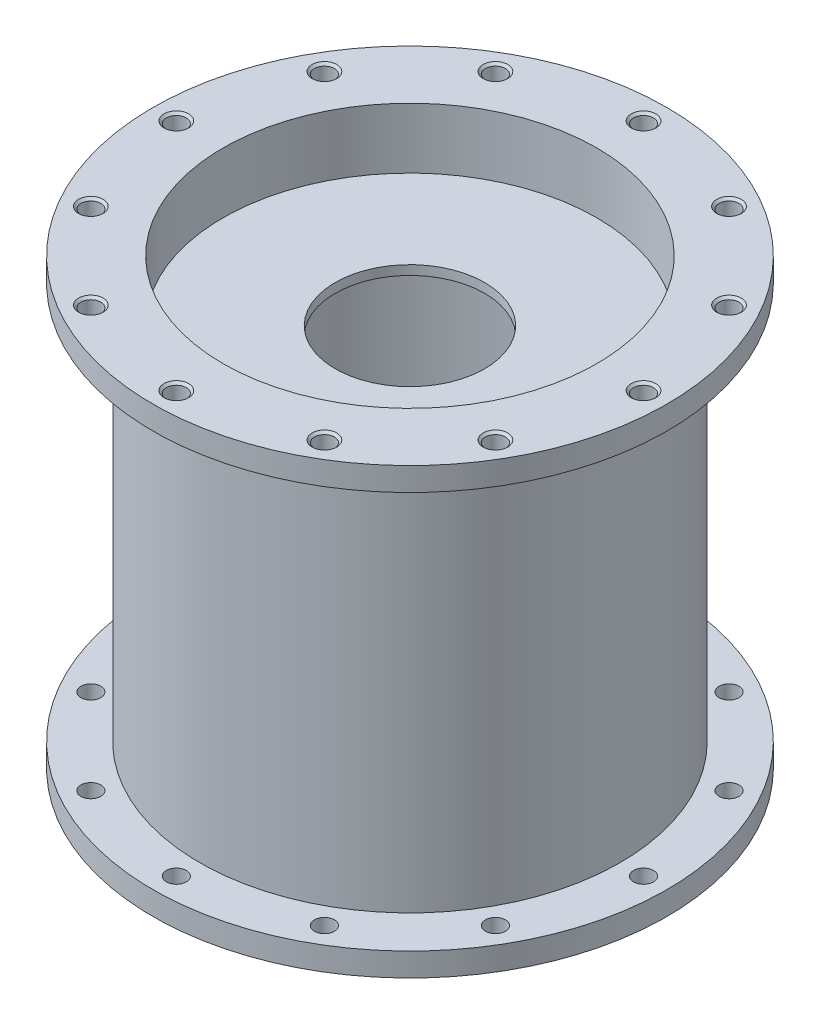
SolidWorks part; units mm, degrees
ref_plane "Front Plane" through (0, 0, 0) normal (0, 0, 1) x (1, 0, 0)
ref_plane "Top Plane" through (0, 0, 0) normal (0, 1, 0) x (1, 0, 0)
ref_plane "Right Plane" through (0, 0, 0) normal (1, 0, 0) x (0, 0, -1)
sketch "Sketch1" plane through (0, 0, 0) normal (1, 0, 0) x (0, 0, -1)
  line L1 (57.15, 6.35) -> (57.15, 114.3)
  line L8 (57.15, 120.65) -> (69.85, 120.65)
  line L9 (69.85, 120.65) -> (69.85, 114.3)
  line L10 (69.85, 114.3) -> (57.15, 114.3)
  line L11 (57.15, 0) -> (69.85, 0)
  line L12 (69.85, 0) -> (69.85, 6.35)
  line L13 (69.85, 6.35) -> (57.15, 6.35)
  line L27 (50.8, 114.3) -> (50.8, 120.65)
  line L28 (50.8, 120.65) -> (57.15, 120.65)
  line L29 (50.8, 6.35) -> (50.8, 0)
  line L30 (50.8, 0) -> (57.15, 0)
  line L31 (50.8, 114.3) -> (50.8, 6.35)
  line L32 (50.8, 0) -> (0, 0) construction
  line L33 (0, 0) -> (0, 6.35) construction
  dimension "D1" = 6.35
  dimension "D2" = 6.35
  dimension "D3" = 12.7
  dimension "D4" = 12.7
  dimension "D5" = 12.7
  dimension "D6" = 12.7
  dimension "D7" = 107.95
  dimension "D8" = 50.8
  dimension "D9" = 6.35
revolve "Chamber" add sketch "Sketch1" angle 360 about L33
sketch "Sketch4" plane through (0, 0, 0) normal (1, 0, 0) x (0, 0, -1)
  line L0 (0, 0) -> (0, 120.65) construction
  line L1 (50.8, 120.65) -> (-50.8, 120.65) construction
  line L3 (50.8, 104.2017) -> (20.32, 104.2017)
  line L7 (50.8, 104.2017) -> (50.8, 101.6617)
  line L8 (0, 60.325) -> (57.15, 60.325) construction
  line L9 (20.32, 104.2017) -> (20.32, 101.6617)
  line L10 (50.8, 16.4483) -> (20.32, 16.4483)
  line L11 (50.8, 16.4483) -> (50.8, 18.9883)
  line L12 (50.8, 18.9883) -> (20.32, 18.9883)
  line L13 (20.32, 16.4483) -> (20.32, 18.9883)
  line L14 (50.8, 101.6617) -> (20.32, 101.6617)
  point P9 (50.7813, 15.9134)
  point P10 (50.342, 18.9883)
  dimension "D1" = 2.54
  dimension "D2" = 30.48
revolve "Turbulence Rings" add sketch "Sketch4" angle 360 about L0
sketch "Sketch5" plane through (0, 120.65, 0) normal (0, 1, 0) x (1, 0, 0)
  line L0 (0, 0) -> (-63.5, 0) construction
  line L1 (0, 0) -> (-54.9926, 31.75) construction
  circle A0 centre (0, 0) radius 63.5 construction
  point P0 (0, 0)
  point P5 (-63.5, 0)
  point P9 (-54.9926, 31.75)
  point P10 (-31.75, 54.9926)
  point P11 (0, 63.5)
  point P12 (31.75, 54.9926)
  point P13 (54.9926, 31.75)
  point P14 (63.5, 0)
  point P15 (54.9926, -31.75)
  point P16 (31.75, -54.9926)
  point P17 (0, -63.5)
  point P18 (-31.75, -54.9926)
  point P19 (-54.9926, -31.75)
  point P20 (0, 0)
  dimension "D1" = 30
  dimension "D2" = 12
hole_wizard "#3 (0.213) Diameter Hole1" positions "Sketch5" profile "Sketch6" hole size "#3" standard "ANSI Inch" end condition through all
sketch "Sketch6" plane through (-54.9926, 120.65, 31.75) normal (1, 0, 0) x (0, 0, 1)
  line L0 (0, 0) -> (0, 120.65)
  line L1 (0, 120.65) -> (3.3401, 120.65)
  line L2 (2.7051, 120.015) -> (2.7051, 0.635)
  line L3 (2.7051, 0.635) -> (3.3401, 0)
  line L5 (3.3401, 0) -> (0, 0)
  line L6 (-2.7051, 0.635) -> (-3.3401, 0) construction
  line L7 (3.3401, 120.65) -> (2.7051, 120.015)
  line L8 (-3.3401, 120.65) -> (-2.7051, 120.015) construction
  line L11 (0, -6.35) -> (0, 107.95) construction
  dimension "Thru Hole Dia." = 5.4102
  dimension "Thru Hole Depth" = 120.65
  dimension "Near C'Sink Dia." = 6.6802
  dimension "Near C'Sink Angle" = 90
  dimension "Far C'Sink Dia." = 6.6802
  dimension "Far C'Sink Angle" = 90
equation "\"Thickness of Material\"= 0.3in"
equation "\"Chamber Length\"= 4.25in"
equation "\"Flange Length\"= 0.5in"
equation "\"Chamber Wall Thickness\"= 0.25in"
equation "\"Ring Length\"= 1.2in"
equation "\"Ring Thickness\"= 0.1in"
equation "\"Number of Rings\" = 2"
equation "\"Chamber Radius\"= 2in"
